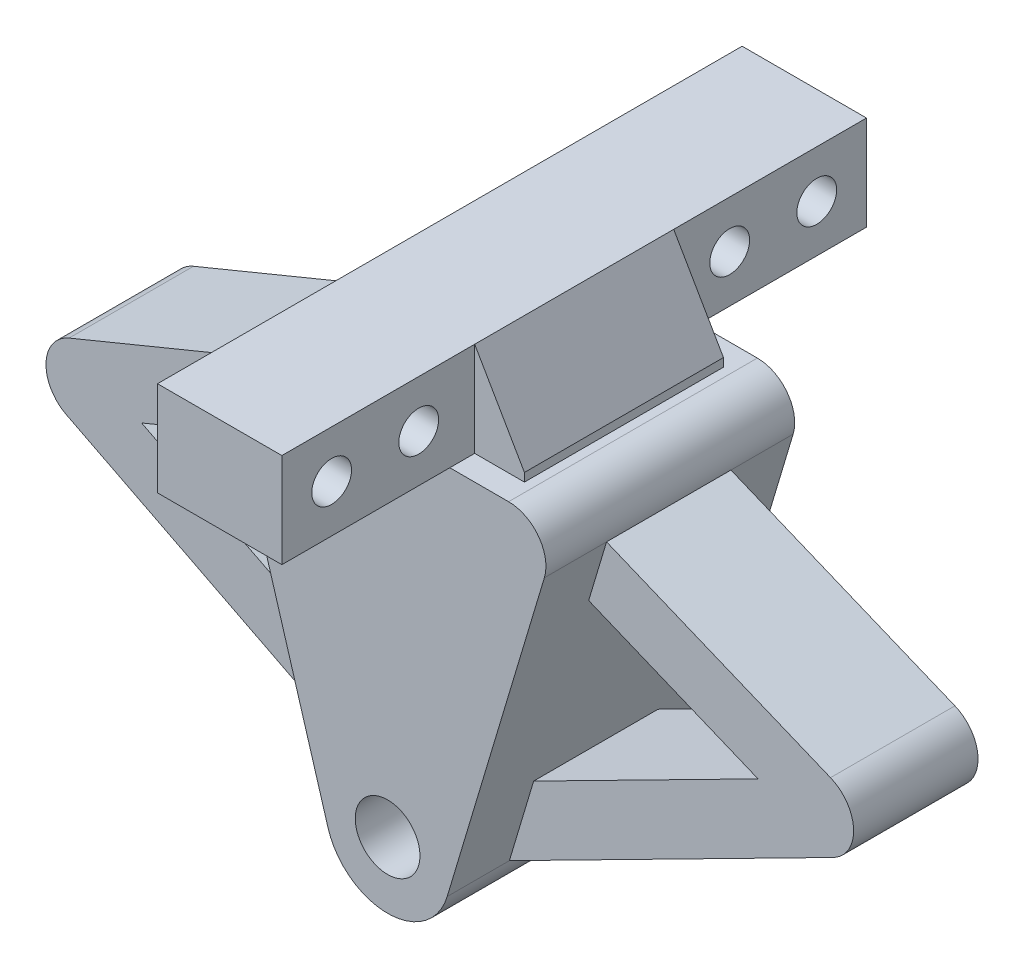
SolidWorks part; units mm, degrees
ref_plane "前视基准面" through (0, 0, 0) normal (0, 0, 1) x (1, 0, 0)
ref_plane "上视基准面" through (0, 0, 0) normal (0, 1, 0) x (1, 0, 0)
ref_plane "右视基准面" through (0, 0, 0) normal (1, 0, 0) x (0, 0, -1)
sketch "草图1" plane through (0, 0, 0) normal (1, 0, 0) x (0, 0, -1)
  line L0 (0, 0) -> (-23.5, 0) construction
  line L1 (23.5, -3.8) -> (-23.5, -3.8)
  line L2 (23.5, -3.8) -> (23.5, 3.8)
  line L3 (23.5, 3.8) -> (-23.5, 3.8)
  line L4 (-23.5, -3.8) -> (-23.5, 3.8)
  line L5 (23.5, -3.8) -> (-23.5, 3.8) construction
  line L6 (23.5, 3.8) -> (-23.5, -3.8) construction
  line L7 (0, 0) -> (0, -7.5593) construction
  circle A0 centre (-19.5, 0) radius 1.6
  circle A1 centre (-12.5, 0) radius 1.6
  circle A4 centre (12.5, 0) radius 1.6
  circle A5 centre (19.5, 0) radius 1.6
  point P0 (0, 0)
  dimension "D1" = 47
  dimension "D2" = 7.6
  dimension "D3" = 7
  dimension "D4" = 12.5
extrude "凸台-拉伸1" add sketch "草图1" along normal mid plane 10
sketch "草图4" plane through (0, 0, 0) normal (0, 0, 1) x (1, 0, 0)
  line L0 (0, 0) -> (0, 7.8238) construction
  line L1 (5, 3.8) -> (9, 3.8)
  line L2 (5, 3.8) -> (5, -3.8)
  line L3 (5, -3.8) -> (9, -3.8)
  line L4 (9, 3.8) -> (9, -3.8)
  line L5 (-9, 3.8) -> (-9, -3.8)
  line L6 (-5, -3.8) -> (-9, -3.8)
  line L7 (-5, 3.8) -> (-5, -3.8)
  line L8 (-5, 3.8) -> (-9, 3.8)
extrude "凸台-拉伸3" add sketch "草图4" along normal mid plane 16
sketch "草图3" plane through (0, 0, 0) normal (0, 0, 1) x (1, 0, 0)
  line L0 (0, -3.8) -> (0, -9.8882) construction
  line L2 (0, -3.8) -> (-13.7569, -3.8)
  line L3 (5, -3.8) -> (-5, -3.8) construction
  line L4 (-13.7569, -3.8) -> (0, -49.7667)
  line L5 (0, -49.7667) -> (13.7569, -3.8)
  line L6 (13.7569, -3.8) -> (0, -3.8)
  circle A0 centre (0, -32.0203) radius 2.6
  point P8 (0, -25.5693)
  point P13 (13.7569, -3.8)
  point P14 (0, -30.6579)
  point P15 (0, -20.8029)
  point P16 (0, -35.2064)
  point P17 (0, -24.0879)
  point P18 (0, -20.2975)
  point P19 (0, -30.4053)
  point P20 (0, -42.5269)
  point P21 (0, -28.9301)
  point P22 (0, -45.0873)
  point P23 (0, -49.7667)
  point P24 (0, -32.0203)
extrude "凸台-拉伸2" add sketch "草图3" along normal mid plane 20
fillet "圆角1" radius 5 1 edges at (0, -49.7667, 0)
chamfer "倒角1" distance 4 angle 60 2 edges at (-9, 3.8, 0) (9, 3.8, 0) first distance on face at (0, 3.8, 0)
fillet "圆角2" radius 3 2 edges at (-13.7569, -3.8, 0) (13.7569, -3.8, 0)
sketch "草图5" plane through (0, 0, 0) normal (0, 0, 1) x (1, 0, 0)
  line L0 (-12.6016, -7.6601) -> (-36.6477, -17.5625)
  line L1 (-36.6477, -17.5625) -> (-4.7901, -33.7614)
  line L2 (-12.6016, -7.6601) -> (-11.1642, -12.4632)
  line L3 (-24.7828, -18.0714) -> (-11.1642, -12.4632)
  line L4 (-24.7828, -18.0714) -> (-6.7401, -27.2457)
  line L5 (-6.7401, -27.2457) -> (-4.7901, -33.7614)
  line L6 (-12.6016, -7.6601) -> (-4.7901, -33.7614) construction
  point P3 (-6.7401, -27.2457)
  point P9 (-36.6477, -17.5625)
extrude "凸台-拉伸4" add sketch "草图5" along normal mid plane 10
fillet "圆角3" radius 3 1 edges at (-36.6477, -17.5625, 0)
mirror "镜向1" about plane through (0, 0, 0) normal (1, 0, 0) of "圆角3", "凸台-拉伸4"
